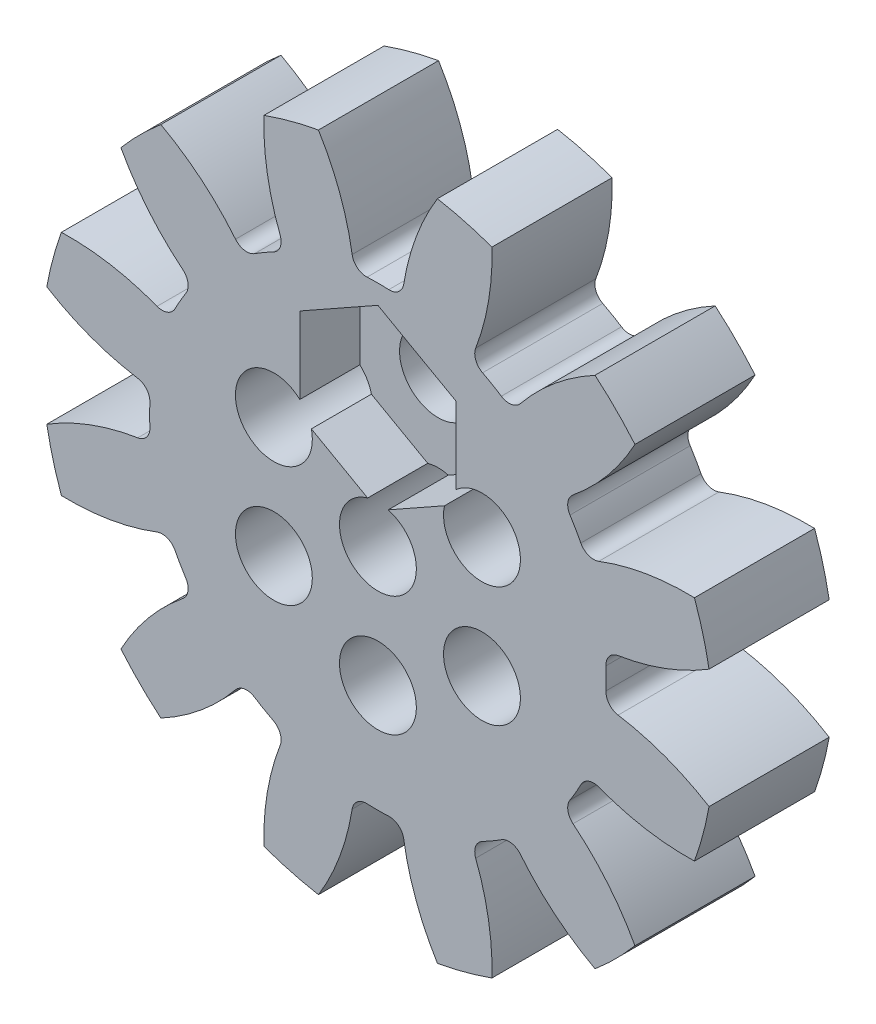
SolidWorks part; units mm, degrees
ref_plane "Front Plane" through (0, 0, 0) normal (0, 0, 1) x (1, 0, 0)
ref_plane "Top Plane" through (0, 0, 0) normal (0, 1, 0) x (1, 0, 0)
ref_plane "Right Plane" through (0, 0, 0) normal (1, 0, 0) x (0, 0, -1)
sketch "Sketch1" plane through (0, 0, 0) normal (0, 0, 1) x (1, 0, 0)
  circle A0 centre (0, 0) radius 12
  circle A1 centre (0, 0) radius 9.5
  circle A2 centre (0, 0) radius 14
  dimension "D1" = 24
  dimension "D2" = 28
  dimension "D3" = 4.5
extrude "Boss-Extrude1" add sketch "Sketch1" along normal mid plane 5 contours A2
sketch "Sketch2" plane through (0, 0, 0) normal (0, 0, 1) x (1, 0, 0)
  line L0 (0, 0) -> (0, 14) construction
  line L1 (-0.9997, 9.4472) -> (0, 0) construction
  line L2 (-1.5663, 11.8973) -> (1.5663, 11.8973) construction
  line L3 (0, 7.5939) -> (-2.7213, 15.0705) construction
  line L4 (0, 0) -> (3.6235, 13.523) construction
  line L5 (1.5663, 11.8973) -> (4.5922, 11.0866) construction
  circle A0 centre (0, 0) radius 14 construction
  arc A1 (-3.3146, 14.9512) -> (-0.9997, 9.4472) centre (-11.2897, 8.3583) cw
  arc A2 (3.3146, 14.9512) -> (0.9997, 9.4472) centre (11.2897, 8.3583) ccw
  arc A3 (3.3146, 14.9512) -> (-3.3146, 14.9512) centre (0, 0) ccw
  arc A4 (0.9997, 9.4472) -> (-0.9997, 9.4472) centre (0, 0) ccw
  circle A6 centre (0, 0) radius 9.5 construction
  circle A7 centre (0, 0) radius 12 construction
  dimension "D1" = 20
  dimension "D2" = 15
extrude "Cut-Extrude1" cut sketch "Sketch2" against normal through all both and the other way through all
fillet "Fillet1" radius 0.6 1 edges at (-0.9997, 9.4472, 0) type face fillet first side face at (-1.6166, 11.6546, 0) second side face at (0, 9.4736, 0)
fillet "Fillet2" radius 0.6 1 edges at (0.9997, 9.4472, 0) type face fillet first side face at (1.6166, 11.6546, 0) second side face at (0.2746, 9.4821, 0)
sketch "Sketch3" plane through (0, 0, 2.5) normal (0, 0, 1) x (1, 0, 0)
pattern_circular "CirPattern2" count 12 over 360 about axis through (0, 0, 2.5) along (0, 0, 1) of "Fillet1", "Cut-Extrude1", "Fillet2"
sketch "Sketch4" plane through (0, 0, 2.5) normal (0, 0, 1) x (1, 0, 0)
  line L0 (0, 0) -> (0, 8.1574) construction
  circle A0 centre (0, 0) radius 1.5
  circle A1 centre (0, 5) radius 1.5
  circle A2 centre (4.3301, 2.5) radius 1.5
  circle A3 centre (4.3301, -2.5) radius 1.5
  circle A4 centre (0, -5) radius 1.5
  circle A5 centre (-4.3301, -2.5) radius 1.5
  circle A6 centre (-4.3301, 2.5) radius 1.5
  point P18 (0, 0)
  dimension "D1" = 3
  dimension "D2" = 3
  dimension "D3" = 5
  dimension "D4" = 6
extrude "Cut-Extrude2" cut sketch "Sketch4" against normal through all both and the other way through all
sketch "Sketch5" plane through (0, 0, 2.5) normal (0, 0, 1) x (1, 0, 0)
  circle A0 centre (0, 5) radius 1.6
  circle A1 centre (-4.3301, -2.5) radius 1.5
  circle A2 centre (-4.3301, -2.5) radius 1.5 construction
  circle A3 centre (0, -5) radius 1.5
  circle A4 centre (0, -5) radius 1.5 construction
  circle A5 centre (4.3301, -2.5) radius 1.5
  circle A6 centre (4.3301, -2.5) radius 1.5 construction
  circle A7 centre (4.3301, 2.5) radius 1.5
  circle A8 centre (4.3301, 2.5) radius 1.5 construction
  circle A9 centre (0, 5) radius 1.5
  circle A10 centre (0, 5) radius 1.5 construction
  circle A11 centre (0, 0) radius 1.5
  circle A12 centre (0, 0) radius 1.5 construction
  circle A13 centre (-4.3301, 2.5) radius 1.5
  circle A14 centre (-4.3301, 2.5) radius 1.5 construction
  circle A15 centre (4.3301, 2.5) radius 1.6
  circle A16 centre (4.3301, -2.5) radius 1.6
  circle A17 centre (0, -5) radius 1.6
  circle A18 centre (0, 0) radius 1.6
  circle A19 centre (-4.3301, -2.5) radius 1.6
  circle A20 centre (-4.3301, 2.5) radius 1.6
  dimension "D8" = 3.2
  dimension "D1" = 0
  dimension "D2" = 0
  dimension "D3" = 0
  dimension "D4" = 0
  dimension "D5" = 0
  dimension "D6" = 0
  dimension "D7" = 0
extrude "Cut-Extrude3" cut sketch "Sketch5" against normal through all
sketch "Sketch6" plane through (0, 0, 2.5) normal (0, 0, 1) x (1, 0, 0)
  line L0 (0, 5) -> (-2.75, 5)
  line L1 (0, 5) -> (2.75, 5)
  line L2 (-2.75, 6.5777) -> (-2.75, 3.4223) construction
  line L3 (2.75, 6.5777) -> (2.75, 3.4223) construction
  line L4 (-2.75, 6.5777) -> (0, 8.125) construction
  line L5 (0, 8.125) -> (2.75, 6.5777) construction
  line L6 (2.75, 3.4223) -> (0, 1.875) construction
  line L7 (0, 1.875) -> (-2.75, 3.4223) construction
  line L8 (0, 1.3013) -> (-3.25, 3.1299)
  line L9 (-3.25, 6.8701) -> (-3.25, 3.1299)
  line L10 (-3.25, 6.8701) -> (0, 8.6987)
  line L11 (0, 8.6987) -> (3.25, 6.8701)
  line L12 (3.25, 6.8701) -> (3.25, 3.1299)
  line L13 (3.25, 3.1299) -> (0, 1.3013)
  point P4 (-2.75, 5)
  point P7 (0, 0)
  point P12 (-3, 6.5231)
  point P13 (-0.1868, 7.9168)
  point P14 (2.75, 5)
  point P15 (0, 8.1412)
  dimension "D1" = 5.5
  dimension "D2" = 6.25
  dimension "D3" = 0.5
extrude "Cut-Extrude4" cut sketch "Sketch6" against normal blind 2.5 contours L13 L12 L11 L10 L9 L8 region at (-1.5767, 2.3014, 2.5)
equation "\"Number of Teeth\"= 12"
equation "\"Module\"= 2mm"
equation "\"D2@Sketch2\"=180 / \"Number of Teeth\""
equation "\"D1@Sketch1\"= \"Module\" * \"Number of Teeth\""
equation "\"D2@Sketch1\"=(\"Number of Teeth\" + 2) * \"Module\""
equation "\"D3@Sketch1\"= \"Module\" * 2.25"
equation "\"D1@CirPattern2\"= \"Number of Teeth\""
